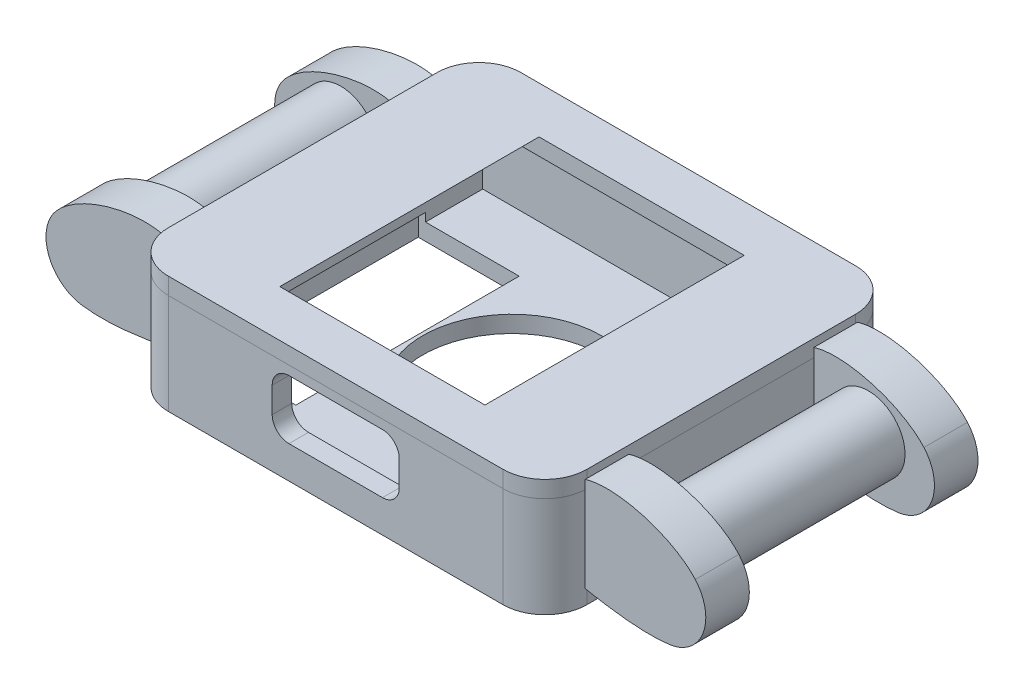
SolidWorks part; units mm, degrees
ref_plane "Front Plane" through (0, 0, 0) normal (0, 0, 1) x (1, 0, 0)
ref_plane "Top Plane" through (0, 0, 0) normal (0, 1, 0) x (1, 0, 0)
ref_plane "Right Plane" through (0, 0, 0) normal (1, 0, 0) x (0, 0, -1)
sketch "Sketch1" plane through (0, 0, 0) normal (0, 1, 0) x (1, 0, 0)
  line L1 (-24.9882, -21.0521) -> (24.9882, -21.0521)
  line L2 (-24.9882, -21.0521) -> (-24.9882, 21.0521)
  line L3 (-24.9882, 21.0521) -> (24.9882, 21.0521)
  line L4 (24.9882, -21.0521) -> (24.9882, 21.0521)
  line L5 (-24.9882, -21.0521) -> (24.9882, 21.0521) construction
  line L6 (-24.9882, 21.0521) -> (24.9882, -21.0521) construction
  circle A0 centre (0, 0) radius 10.6476
  point P0 (0, 0)
extrude "Boss-Extrude2" add sketch "Sketch1" along normal blind 2 contours A0 | L2 L1 L4 L3
sketch "Sketch2" plane through (0, 2, 0) normal (0, 1, 0) x (1, 0, 0)
  line L1 (-24.9882, -21.0521) -> (24.9882, -21.0521)
  line L2 (-24.9882, -21.0521) -> (-24.9882, 21.0521)
  line L3 (-24.9882, 21.0521) -> (24.9882, 21.0521)
  line L4 (24.9882, -21.0521) -> (24.9882, 21.0521)
  line L5 (-24.9882, -21.0521) -> (24.9882, 21.0521) construction
  line L6 (-24.9882, 21.0521) -> (24.9882, -21.0521) construction
  line L7 (-22.2195, -18.7196) -> (22.2195, -18.7196)
  line L8 (-22.2195, -18.7196) -> (-22.2195, 18.7196)
  line L9 (-22.2195, 18.7196) -> (22.2195, 18.7196)
  line L10 (22.2195, -18.7196) -> (22.2195, 18.7196)
  line L11 (-22.2195, -18.7196) -> (22.2195, 18.7196) construction
  line L12 (-22.2195, 18.7196) -> (22.2195, -18.7196) construction
  point P0 (0, 0)
  point P7 (0, 0)
extrude "Boss-Extrude3" add sketch "Sketch2" along normal blind 10
sketch "Sketch3" plane through (0, 0, 21.0521) normal (0, 0, 1) x (1, 0, 0)
  line L0 (-7.5856, 5.8777) -> (-7.5856, 8.9175)
  line L3 (5.5856, 10.9175) -> (-5.5856, 10.9175)
  line L6 (2.6942, 3.8777) -> (0, 0) construction
  line L9 (5.5856, 3.8777) -> (-5.5856, 3.8777)
  line L11 (0, 0) -> (-7.5856, 3.8777) construction
  line L12 (7.5856, 3.8777) -> (0, 0) construction
  line L14 (0, 0) -> (-2.6942, 3.8777) construction
  line L15 (7.5856, 5.8777) -> (7.5856, 8.9175)
  arc A0 (-5.5856, 3.8777) -> (-7.5856, 5.8777) centre (-5.5856, 5.8777) cw
  arc A1 (7.5856, 5.8777) -> (5.5856, 3.8777) centre (5.5856, 5.8777) cw
  arc A2 (7.5856, 8.9175) -> (5.5856, 10.9175) centre (5.5856, 8.9175) ccw
  arc A3 (-5.5856, 10.9175) -> (-7.5856, 8.9175) centre (-5.5856, 8.9175) ccw
  point P0 (0, 0)
  point P6 (0, 0)
  dimension "D1" = 2
extrude "Cut-Extrude1" cut sketch "Sketch3" against normal blind 10
sketch "Sketch4" plane through (0, 12, 0) normal (0, 1, 0) x (1, 0, 0)
  line L1 (-24.9882, -21.0521) -> (24.9882, -21.0521)
  line L2 (-24.9882, -21.0521) -> (-24.9882, 21.0521)
  line L3 (-24.9882, 21.0521) -> (24.9882, 21.0521)
  line L4 (24.9882, -21.0521) -> (24.9882, 21.0521)
  line L5 (-24.9882, -21.0521) -> (24.9882, 21.0521) construction
  line L6 (-24.9882, 21.0521) -> (24.9882, -21.0521) construction
  point P0 (0, 0)
extrude "Boss-Extrude4" add sketch "Sketch4" along normal blind 2 separate body
sketch "Sketch5" plane through (0, 14, 0) normal (0, 1, 0) x (1, 0, 0)
  line L1 (-11.2486, -15.4802) -> (11.2486, -15.4802)
  line L2 (-11.2486, -15.4802) -> (-11.2486, 15.4802)
  line L3 (-11.2486, 15.4802) -> (11.2486, 15.4802)
  line L4 (11.2486, -15.4802) -> (11.2486, 15.4802)
  line L5 (-11.2486, -15.4802) -> (11.2486, 15.4802) construction
  line L6 (-11.2486, 15.4802) -> (11.2486, -15.4802) construction
  point P0 (0, 0)
extrude "Cut-Extrude2" cut sketch "Sketch5" against normal blind 3
sketch "Sketch6" plane through (0, 0, 0) normal (0, -1, 0) x (1, 0, 0)
  line L1 (-23.0864, 14.7839) -> (-11.0343, 14.7839)
  line L2 (-23.0864, 14.7839) -> (-23.0864, -11.8914)
  line L3 (-23.0864, -11.8914) -> (-11.0343, -11.8914)
  line L4 (-11.0343, 14.7839) -> (-11.0343, -11.8914)
extrude "Cut-Extrude3" cut sketch "Sketch6" against normal blind 3
fillet "Fillet3" radius 5 1 edges at (-24.9882, 6, 21.0521)
fillet "Fillet4" radius 5 2 edges at (-24.9882, 13, -21.0521) (-24.9882, 13, 21.0521)
fillet "Fillet5" radius 5 3 edges at (24.9882, 6, 21.0521) (24.9882, 6, -21.0521) (-24.9882, 6, -21.0521)
fillet "Fillet6" radius 5 2 edges at (24.9882, 13, -21.0521) (24.9882, 13, 21.0521)
chamfer "Chamfer1" distance 3 angle 45 2 edges at (-11.2486, 12, 0) (11.2486, 12, 0)
ref_plane "Plane1" through (0, 0, 0) normal (1, 0, 0) x (0, 0, -1)
ref_plane "Plane2" through (0, 0, 0) normal (0, 0, -1) x (-1, 0, 0)
sketch "Sketch7" plane through (0, 0, 0) normal (0, 0, -1) x (-1, 0, 0)
  circle A0 centre (-31.5054, 7.46) radius 4.3766
extrude "Boss-Extrude5" add sketch "Sketch7" along normal up to vertex (16.0521 mm away) and the other way up to vertex (16.0521 mm away) separate body up to point (24.9882, 0, -16.0521) other way up to point (24.9882, 12, 16.0521)
mirror "Mirror1" about plane through (0, 0, 0) normal (1, 0, 0) of bodies 108
sketch "Sketch8" plane through (0, 0, -16.0521) normal (0, 0, -1) x (-1, 0, 0)
  line L0 (-24.6323, 12.9515) -> (-24.0738, 1.9584)
  arc A0 (-38.1385, 9.2887) -> (-35.058, 1.0188) centre (-34.3947, 5.9746) ccw
  spline S0 degree 3 poles (-24.6323, 12.9515) (-28.4371, 14.3629) (-35.3847, 12.3996) (-38.1385, 9.2887) knots 0 0 0 0 0.766664 0.766664 0.766664 0.766664
  spline S1 degree 3 poles (-24.0738, 1.9584) (-28.7572, 0.9787) (-32.4186, 0.6655) (-35.058, 1.0188) knots 0 0 0 0 0.375825 0.375825 0.375825 0.375825
  dimension "D1" = 5
extrude "Boss-Extrude7" add sketch "Sketch8" along normal blind 0.2 and the other way blind 5 separate body
mirror "Mirror3" about plane through (0, 0, 0) normal (0, 0, -1) of bodies 111
mirror "Mirror4" about plane through (0, 0, 0) normal (1, 0, 0) of bodies 111 112
